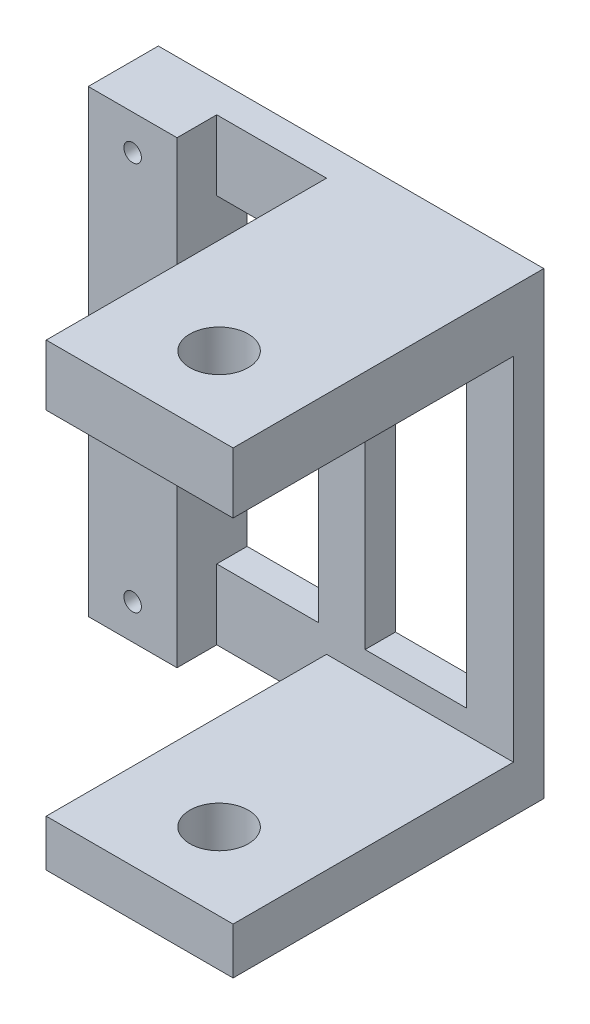
SolidWorks part; units mm, degrees
ref_plane "前视基准面" through (0, 0, 0) normal (0, 0, 1) x (1, 0, 0)
ref_plane "上视基准面" through (0, 0, 0) normal (0, 1, 0) x (1, 0, 0)
ref_plane "右视基准面" through (0, 0, 0) normal (1, 0, 0) x (0, 0, -1)
sketch "草图2" plane through (0, 0, 0) normal (0, 0, 1) x (1, 0, 0)
  line L3 (-9.15, -9.825) -> (7.35, -9.825)
  line L4 (7.35, 9.825) -> (7.35, -9.825)
  line L5 (0, 0) -> (2.4933, 0) construction
  line L6 (0, 0) -> (0, -3.9686) construction
  line L15 (-9.15, 9.825) -> (7.35, 9.825)
  line L16 (-5.35, 6.825) -> (-1, 6.825)
  line L17 (-5.35, 6.825) -> (-5.35, -6.825)
  line L18 (-5.35, -6.825) -> (-1, -6.825)
  line L20 (-9.15, 9.825) -> (-9.15, -9.825)
  line L21 (1, 6.825) -> (5.35, 6.825)
  line L23 (1, -6.825) -> (1, 6.825)
  line L25 (-1, -6.825) -> (-1, 6.825)
  line L26 (5.35, 6.825) -> (5.35, -6.825)
  line L28 (1, -6.825) -> (5.35, -6.825)
  point P0 (0, 0)
  dimension "D1" = 16.5
  dimension "D3" = 19.65
  dimension "D4" = 3.8
  dimension "D5" = 3
  dimension "D6" = 2
  dimension "D8" = 3
  dimension "D9" = 2
extrude "凸台-拉伸1" add sketch "草图2" along normal blind 1.3
sketch "草图3" plane through (0, 0, 1.3) normal (0, 0, 1) x (1, 0, 0)
  line L1 (-0.65, 9.825) -> (7.35, 9.825)
  line L2 (-0.65, 9.825) -> (-0.65, 7.225)
  line L3 (-0.65, 7.225) -> (7.35, 7.225)
  line L4 (7.35, 9.825) -> (7.35, 7.225)
  line L5 (7.35, -9.825) -> (7.35, 9.825) construction
  line L6 (-0.65, -7.825) -> (7.35, -7.825)
  line L8 (-0.65, -9.825) -> (7.35, -9.825)
  line L9 (7.35, -7.825) -> (7.35, -9.825)
  line L10 (-9.15, -9.825) -> (7.35, -9.825) construction
  line L11 (-0.65, -7.825) -> (-0.65, -9.825)
  line L12 (7.35, 9.825) -> (-9.15, 9.825) construction
  dimension "D1" = 2
  dimension "D2" = 2.6
  dimension "D3" = 8
  dimension "D4" = 8
extrude "凸台-拉伸2" add sketch "草图3" along normal blind 12
sketch "草图10" plane through (0, 0, 1.3) normal (0, 0, 1) x (1, 0, 0)
  line L0 (-9.15, 9.825) -> (-9.15, -9.825) construction
  line L1 (-9.15, 9.825) -> (-5.35, 9.825)
  line L2 (-9.15, 9.825) -> (-9.15, -9.825)
  line L3 (-9.15, -9.825) -> (-5.35, -9.825)
  line L4 (-5.35, 9.825) -> (-5.35, -9.825)
  line L5 (-0.65, 9.825) -> (-9.15, 9.825) construction
  line L6 (-9.15, -9.825) -> (-0.65, -9.825) construction
  line L7 (-5.35, 6.825) -> (-5.35, -6.825) construction
extrude "凸台-拉伸4" add sketch "草图10" along normal blind 1.7
sketch "草图9" plane through (0, 0, 1.3) normal (0, 0, 1) x (1, 0, 0)
  line L0 (-0.65, 9.825) -> (-5.35, 9.825) construction
  line L1 (-9.15, 9.825) -> (-9.15, -9.825) construction
  line L2 (-5.35, -9.825) -> (-0.65, -9.825) construction
  circle A0 centre (-7.25, 8.325) radius 0.375
  circle A1 centre (-7.25, -8.325) radius 0.375
  dimension "D1" = 0.75
  dimension "D2" = 0.75
  dimension "D3" = 1.5
  dimension "D4" = 1.9
  dimension "D5" = 1.5
  dimension "D6" = 1.9
extrude "切除-拉伸2" cut sketch "草图9" against normal up to next from surface starting at face at (-7.25, 0, 3)
sketch "草图11" plane through (0, -9.825, 0) normal (0, -1, 0) x (1, 0, 0)
  circle A0 centre (3.45, 10) radius 1.25
  dimension "D1" = 2.5
extrude "切除-拉伸3" cut sketch "草图11" against normal through all
